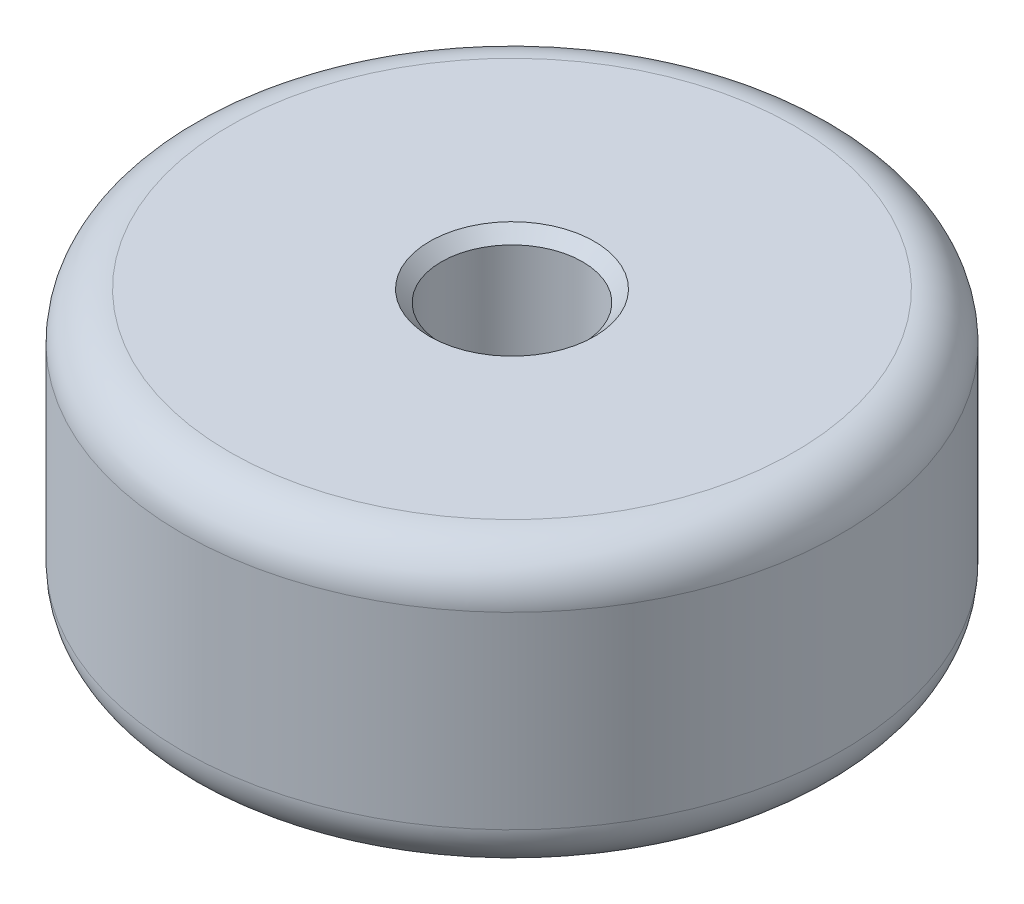
SolidWorks part; units mm, degrees
ref_plane "Front Plane" through (0, 0, 0) normal (0, 0, 1) x (1, 0, 0)
ref_plane "Top Plane" through (0, 0, 0) normal (0, 1, 0) x (1, 0, 0)
ref_plane "Right Plane" through (0, 0, 0) normal (1, 0, 0) x (0, 0, -1)
sketch "Sketch1" plane through (0, 0, 0) normal (0, 1, 0) x (1, 0, 0)
  circle A0 centre (0, 0) radius 11.1125
  circle A1 centre (0, 0) radius 2.3813
  dimension "D1" = 4.7625
  dimension "2.25" = 22.225
extrude "Boss-Extrude1" add sketch "Sketch1" along normal blind 9.525
fillet "Fillet2" radius 1.5875 2 edges at (0, 0, 11.1125) (0, 9.525, 11.1125)
chamfer "Chamfer2" distance 0.3969 angle 45 2 edges at (0, 0, 2.3813) (0, 9.525, 2.3813)
